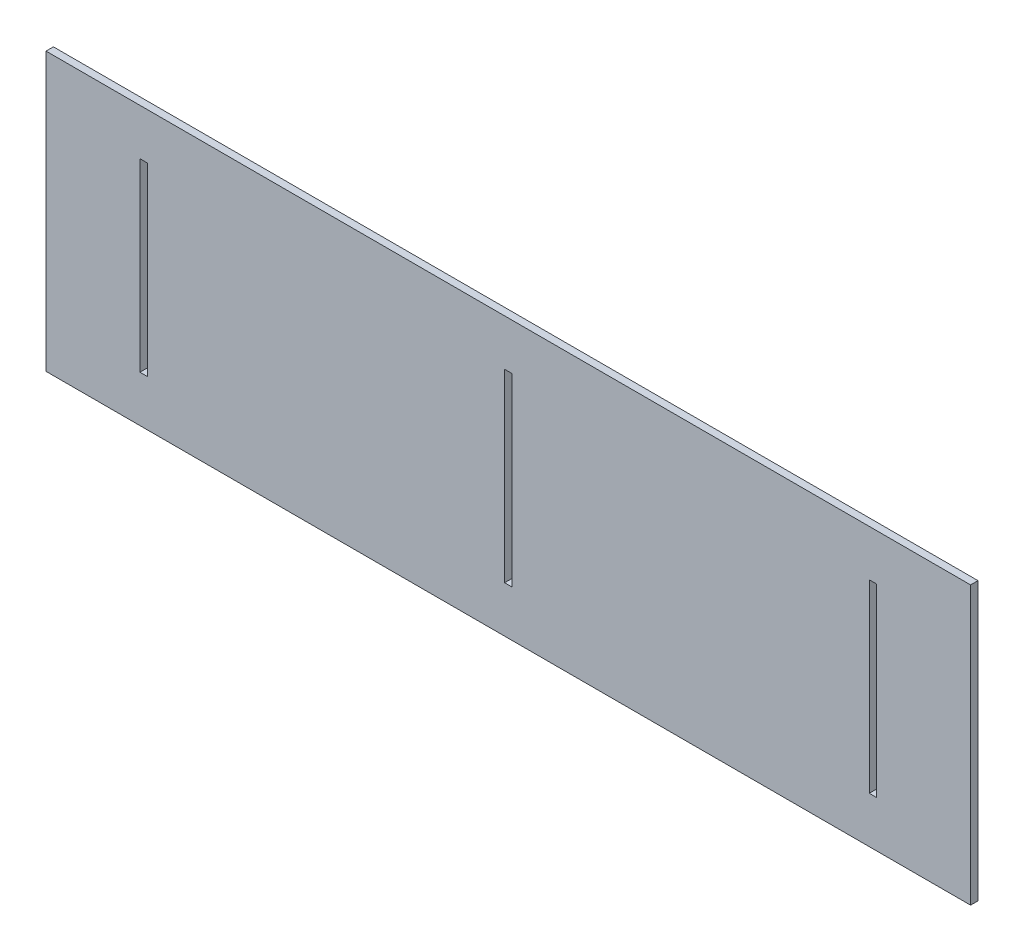
SolidWorks part; units mm, degrees
ref_plane "前视基准面" through (0, 0, 0) normal (0, 0, 1) x (1, 0, 0)
ref_plane "上视基准面" through (0, 0, 0) normal (0, 1, 0) x (1, 0, 0)
ref_plane "右视基准面" through (0, 0, 0) normal (1, 0, 0) x (0, 0, -1)
sketch "草图2" plane through (0, 0, 0) normal (0, 0, 1) x (1, 0, 0)
  line L1 (-73.6818, 78.3847) -> (176.3182, 78.3847)
  line L2 (-73.6818, 78.3847) -> (-73.6818, 3.3847)
  line L3 (-73.6818, 3.3847) -> (176.3182, 3.3847)
  line L4 (176.3182, 78.3847) -> (176.3182, 3.3847)
  dimension "D1" = 250
  dimension "D2" = 75
sketch "草图4" plane through (0, 0, 0) normal (0, 0, 1) x (1, 0, 0)
  line L5 (-73.6818, 78.3847) -> (176.3182, 78.3847) construction
  line L6 (-73.6818, 78.3847) -> (-73.6818, 3.3847) construction
  line L7 (51.3182, 96.8277) -> (51.3182, 60.5853) construction
  line L8 (150.9182, 40.8847) -> (148.9182, 40.8847) construction
  line L9 (149.9182, 15.8847) -> (149.9182, 65.8847) construction
  line L10 (148.9182, 65.8847) -> (148.9182, 15.8847)
  line L11 (-48.2818, 65.8847) -> (-46.2818, 65.8847)
  line L12 (-48.2818, 65.8847) -> (-48.2818, 15.8847)
  line L13 (-48.2818, 15.8847) -> (-46.2818, 15.8847)
  line L14 (-46.2818, 65.8847) -> (-46.2818, 15.8847)
  line L15 (-47.2818, 15.8847) -> (-47.2818, 65.8847) construction
  line L16 (-48.2818, 40.8847) -> (-46.2818, 40.8847) construction
  line L17 (50.3182, 65.8847) -> (52.3182, 65.8847)
  line L18 (50.3182, 65.8847) -> (50.3182, 15.8847)
  line L19 (50.3182, 15.8847) -> (52.3182, 15.8847)
  line L20 (52.3182, 65.8847) -> (52.3182, 15.8847)
  line L21 (51.3182, 15.8847) -> (51.3182, 65.8847) construction
  line L22 (50.3182, 40.8847) -> (52.3182, 40.8847) construction
  line L26 (150.9182, 15.8847) -> (148.9182, 15.8847)
  line L27 (150.9182, 65.8847) -> (150.9182, 15.8847)
  line L28 (150.9182, 65.8847) -> (148.9182, 65.8847)
  point P0 (51.3182, 78.3847)
  point P24 (51.3182, 40.8847)
  point P29 (-47.2818, 40.8847)
  point P34 (51.3182, 40.8847)
  point P35 (149.9182, 40.8847)
  dimension "D1" = 12.5
  dimension "D2" = 50
  dimension "D3" = 2
  dimension "D4" = 50
  dimension "D5" = 2
  dimension "D6" = 25.4
  dimension "D7" = 12.5
extrude "凸台-拉伸3" add sketch "草图2" along normal blind 2
extrude "切除-拉伸1" cut sketch "草图4" against normal blind 2 and the other way blind 2
